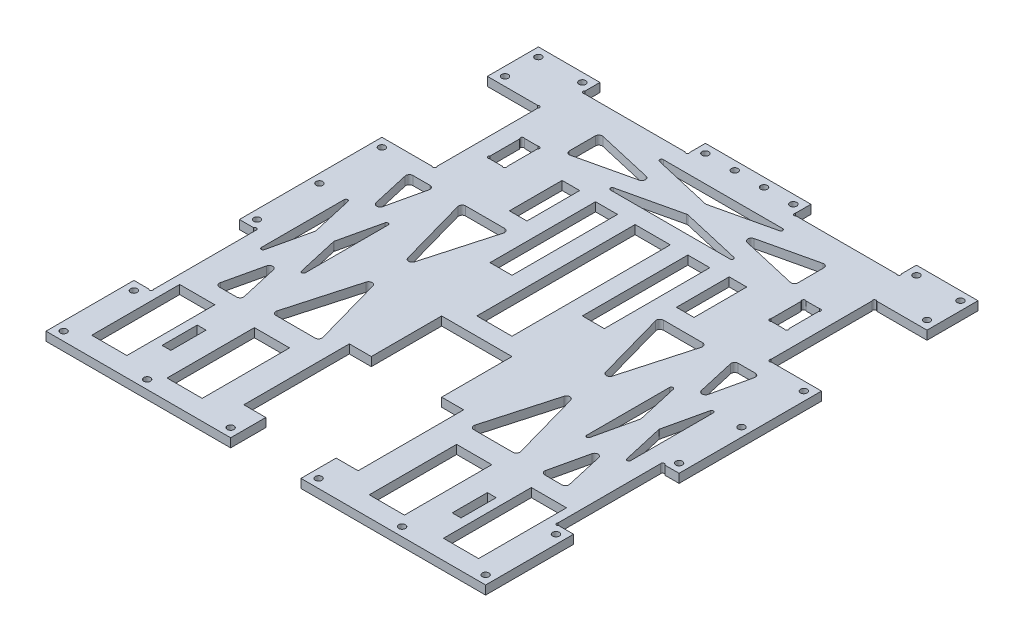
SolidWorks part; units mm, degrees
material "7050-T73510"
ref_plane "Front Plane" through (0, 0, 0) normal (0, 0, 1) x (1, 0, 0)
ref_plane "Top Plane" through (0, 0, 0) normal (0, 1, 0) x (1, 0, 0)
ref_plane "Right Plane" through (0, 0, 0) normal (1, 0, 0) x (0, 0, -1)
sketch "Sketch1" plane through (0, 0, 0) normal (0, 1, 0) x (1, 0, 0)
  line L1 (-158.75, -177.8) -> (158.75, -177.8)
  line L2 (-158.75, -177.8) -> (-158.75, 177.8)
  line L3 (-158.75, 177.8) -> (158.75, 177.8)
  line L4 (158.75, -177.8) -> (158.75, 177.8)
  line L5 (-158.75, -177.8) -> (158.75, 177.8) construction
  line L6 (-158.75, 177.8) -> (158.75, -177.8) construction
  point P0 (0, 0)
  dimension "D1" = 355.6
  dimension "D2" = 317.5
extrude "Boss-Extrude1" add sketch "Sketch1" along normal blind 6.35
sketch "Sketch2" plane through (0, 6.35, 0) normal (0, 1, 0) x (1, 0, 0)
  line L0 (-158.75, -177.8) -> (158.75, -177.8) construction
  line L1 (-25.4, -25.4) -> (25.4, -25.4)
  line L2 (-25.4, -25.4) -> (-25.4, -177.8)
  line L3 (-25.4, -177.8) -> (25.4, -177.8)
  line L4 (25.4, -25.4) -> (25.4, -177.8)
  line L5 (-25.4, -25.4) -> (25.4, -177.8) construction
  line L6 (-25.4, -177.8) -> (25.4, -25.4) construction
  point P0 (0, -101.6)
  dimension "D1" = 152.4
  dimension "D2" = 50.8
extrude "Cut-Extrude1" cut sketch "Sketch2" against normal through all
sketch "Sketch3" plane through (0, 6.35, 0) normal (0, 1, 0) x (1, 0, 0)
  line L0 (158.75, -177.8) -> (158.75, 177.8) construction
  line L5 (146.05, 140.97) -> (120.65, 140.97)
  line L11 (146.05, 140.97) -> (146.05, 64.77)
  line L13 (146.05, 64.77) -> (120.65, 64.77)
  line L15 (120.65, 140.97) -> (120.65, 64.77)
  line L16 (158.75, 177.8) -> (-158.75, 177.8) construction
  line L17 (107.95, 90.17) -> (95.25, 90.17)
  line L18 (107.95, 90.17) -> (107.95, 115.57)
  line L19 (107.95, 115.57) -> (95.25, 115.57)
  line L20 (95.25, 90.17) -> (95.25, 115.57)
  line L21 (0, -3.4925) -> (0, 3.4925) construction
  line L22 (-95.25, 90.17) -> (-95.25, 115.57)
  line L23 (-107.95, 115.57) -> (-95.25, 115.57)
  line L24 (-107.95, 90.17) -> (-107.95, 115.57)
  line L25 (-107.95, 90.17) -> (-95.25, 90.17)
  line L26 (-120.65, 140.97) -> (-120.65, 64.77)
  line L27 (-146.05, 64.77) -> (-120.65, 64.77)
  line L28 (-146.05, 140.97) -> (-146.05, 64.77)
  line L29 (-146.05, 140.97) -> (-120.65, 140.97)
  point P14 (107.95, 102.87)
  point P15 (120.65, 102.87)
  dimension "D1" = 25.4
  dimension "D2" = 12.7
  dimension "D3" = 12.7
  dimension "D4" = 12.7
  dimension "D5" = 25.4
  dimension "D6" = 76.2
  dimension "D7" = 36.83
extrude "Cut-Extrude2" cut sketch "Sketch3" against normal through all contours L5 L15 L13 L11 | L20 L17 L18 L19 | L29 L28 L27 L26 | L24 L25 L22 L23 | L26 L27 L28 L29 region at (133.35, 6.35, -102.87) region at (101.6, 6.35, -102.87) region at (-101.6, 6.35, -102.87) region at (-133.35, 6.35, -102.87)
sketch "Sketch4" plane through (0, 6.35, 0) normal (0, 1, 0) x (1, 0, 0)
  line L0 (-158.75, 177.8) -> (-158.75, -177.8) construction
  line L1 (-158.75, 140.97) -> (-146.05, 140.97)
  line L2 (-158.75, 140.97) -> (-158.75, 64.77)
  line L3 (-158.75, 64.77) -> (-146.05, 64.77)
  line L4 (-146.05, 140.97) -> (-146.05, 64.77)
  line L5 (0, -3.4925) -> (0, 3.4925) construction
  line L6 (-158.75, -114.3) -> (-146.05, -114.3)
  line L7 (-158.75, -114.3) -> (-158.75, -38.1)
  line L8 (-158.75, -38.1) -> (-146.05, -38.1)
  line L9 (-146.05, -114.3) -> (-146.05, -38.1)
  line L10 (158.75, 64.77) -> (146.05, 64.77)
  line L11 (146.05, 140.97) -> (146.05, 64.77)
  line L12 (158.75, 140.97) -> (146.05, 140.97)
  line L13 (158.75, 140.97) -> (158.75, 64.77)
  line L14 (158.75, -38.1) -> (146.05, -38.1)
  line L15 (146.05, -114.3) -> (146.05, -38.1)
  line L16 (158.75, -114.3) -> (146.05, -114.3)
  line L17 (158.75, -114.3) -> (158.75, -38.1)
  line L18 (158.75, 177.8) -> (-158.75, 177.8) construction
  line L19 (114.3, 165.1) -> (38.1, 165.1)
  line L20 (-114.3, 177.8) -> (-38.1, 177.8)
  line L21 (-114.3, 177.8) -> (-114.3, 165.1)
  line L22 (-114.3, 165.1) -> (-38.1, 165.1)
  line L23 (-38.1, 177.8) -> (-38.1, 165.1)
  line L24 (38.1, 177.8) -> (38.1, 165.1)
  line L25 (114.3, 177.8) -> (38.1, 177.8)
  line L26 (114.3, 177.8) -> (114.3, 165.1)
  line L27 (-25.4, -25.4) -> (-25.4, -177.8) construction
  line L28 (-25.4, -152.4) -> (-41.275, -152.4)
  line L29 (-25.4, -152.4) -> (-25.4, -76.2)
  line L30 (-25.4, -76.2) -> (-41.275, -76.2)
  line L31 (-41.275, -152.4) -> (-41.275, -76.2)
  line L32 (-158.75, -177.8) -> (-25.4, -177.8) construction
  line L33 (25.4, 101.6) -> (41.275, 101.6)
  line L34 (-25.4, 25.4) -> (-41.275, 25.4)
  line L35 (-25.4, 25.4) -> (-25.4, 101.6)
  line L36 (-25.4, 101.6) -> (-41.275, 101.6)
  line L37 (-41.275, 25.4) -> (-41.275, 101.6)
  line L38 (41.275, 25.4) -> (41.275, 101.6)
  line L39 (25.4, 25.4) -> (41.275, 25.4)
  line L40 (25.4, 25.4) -> (25.4, 101.6)
  line L41 (25.4, -76.2) -> (41.275, -76.2)
  line L42 (41.275, -152.4) -> (41.275, -76.2)
  line L43 (25.4, -152.4) -> (41.275, -152.4)
  line L44 (25.4, -152.4) -> (25.4, -76.2)
  dimension "D1" = 12.7
  dimension "D2" = 12.7
  dimension "D3" = 76.2
  dimension "D4" = 76.2
  dimension "D5" = 36.83
  dimension "D6" = 215.9
  dimension "D7" = 12.7
  dimension "D8" = 76.2
  dimension "D9" = 76.2
  dimension "D10" = 15.875
  dimension "D11" = 76.2
  dimension "D12" = 25.4
  dimension "D13" = 76.2
  dimension "D14" = 15.875
  dimension "D15" = 203.2
  dimension "D16" = 50.8
extrude "Cut-Extrude3" cut sketch "Sketch4" against normal through all
sketch "Sketch5" plane through (0, 6.35, 0) normal (0, 1, 0) x (1, 0, 0)
  line L0 (-41.275, -76.2) -> (-41.275, -152.4) construction
  line L5 (-41.275, 101.6) -> (-41.275, 25.4) construction
  line L6 (-85.725, -100.33) -> (-60.325, -100.33)
  line L7 (-133.35, -87.63) -> (-101.6, -87.63)
  line L8 (-133.35, -87.63) -> (-133.35, 52.07)
  line L9 (-133.35, 52.07) -> (-101.6, 52.07)
  line L10 (-101.6, -87.63) -> (-101.6, 52.07)
  line L11 (-133.35, -87.63) -> (-101.6, 52.07) construction
  line L12 (-133.35, 52.07) -> (-101.6, -87.63) construction
  line L13 (-82.55, 114.3) -> (82.55, 114.3)
  line L14 (-82.55, 114.3) -> (-82.55, 152.4)
  line L15 (-82.55, 152.4) -> (82.55, 152.4)
  line L16 (82.55, 114.3) -> (82.55, 152.4)
  line L17 (-82.55, 114.3) -> (82.55, 152.4) construction
  line L18 (-82.55, 152.4) -> (82.55, 114.3) construction
  line L23 (0, -3.4925) -> (0, 3.4925) construction
  line L24 (-12.7, -12.7) -> (12.7, -12.7)
  line L25 (-146.05, -114.3) -> (-146.05, -38.1) construction
  line L26 (-53.975, 102.87) -> (-66.675, 102.87)
  line L27 (-53.975, 102.87) -> (-53.975, 64.77)
  line L28 (-158.75, 64.77) -> (-158.75, -38.1) construction
  line L29 (-158.75, 64.77) -> (-120.65, 64.77) construction
  line L30 (-85.725, -100.33) -> (-85.725, -163.4194)
  line L31 (-12.7, -12.7) -> (-12.7, 101.6)
  line L32 (-12.7, 101.6) -> (12.7, 101.6)
  line L33 (12.7, -12.7) -> (12.7, 101.6)
  line L34 (-53.975, 64.77) -> (-66.675, 64.77)
  line L35 (-66.675, 102.87) -> (-66.675, 64.77)
  line L36 (53.975, 64.77) -> (66.675, 64.77)
  line L37 (-25.4, 25.4) -> (-25.4, 101.6) construction
  line L38 (-25.4, 101.6) -> (-41.275, 101.6) construction
  line L39 (-95.25, 90.17) -> (-95.25, 115.57) construction
  line L40 (-114.3, 165.1) -> (-38.1, 165.1) construction
  line L41 (-85.725, -163.4194) -> (-60.325, -163.4194)
  line L42 (-60.325, -100.33) -> (-60.325, -163.4194)
  line L43 (-139.5421, 50.6627) -> (-107.7921, -89.0373)
  line L44 (-127.1579, -89.0373) -> (-95.4079, 50.6627)
  line L45 (66.675, 102.87) -> (66.675, 64.77)
  line L46 (53.975, 102.87) -> (66.675, 102.87)
  line L47 (-83.9779, 146.2126) -> (81.1221, 108.1126)
  line L48 (-81.1221, 108.1126) -> (83.9779, 146.2126)
  line L49 (53.975, 102.87) -> (53.975, 64.77)
  line L50 (-88.9, -16.4414) -> (-53.975, -16.4414) construction
  line L51 (-127.1579, 53.4773) -> (-95.4079, -86.2227)
  line L52 (-139.5421, -86.2227) -> (-107.7921, 53.4773)
  line L53 (-88.9, 52.07) -> (-53.975, 52.07) construction
  line L54 (-88.9, 52.07) -> (-88.9, -84.9527) construction
  line L55 (-81.1221, 158.5874) -> (83.9779, 120.4874)
  line L56 (-83.9779, 120.4874) -> (81.1221, 158.5874)
  line L57 (-139.7, -100.33) -> (-114.3, -100.33)
  line L58 (-139.7, -100.33) -> (-139.7, -163.83)
  line L59 (-139.7, -163.83) -> (-114.3, -163.83)
  line L60 (-114.3, -100.33) -> (-114.3, -163.83)
  line L61 (-88.9, -84.9527) -> (-53.975, -84.9527)
  line L62 (-53.975, 52.07) -> (-53.975, -84.9527) construction
  line L63 (-107.95, -144.78) -> (-101.6, -144.78)
  line L64 (-107.95, -144.78) -> (-107.95, -119.38)
  line L65 (-107.95, -119.38) -> (-101.6, -119.38)
  line L66 (-101.6, -144.78) -> (-101.6, -119.38)
  line L67 (-107.95, -144.78) -> (-101.6, -119.38) construction
  line L68 (-107.95, -119.38) -> (-101.6, -144.78) construction
  line L69 (-88.9, -84.9527) -> (-71.4375, -22.7914)
  line L70 (-71.4375, -22.7914) -> (-53.975, -84.9527)
  line L71 (-88.9, 52.07) -> (-53.975, 52.07)
  line L72 (-88.9, 52.07) -> (-71.4375, -10.0914)
  line L73 (-71.4375, -10.0914) -> (-53.975, 52.07)
  point P5 (-117.475, -17.78)
  point P10 (0, 133.35)
  point P15 (0, 44.45)
  point P34 (-104.775, -132.08)
  point P45 (-33.3375, 101.6)
  point P87 (-114.3, -132.08)
  dimension "D3" = 12.7
  dimension "D4" = 19.05
  dimension "D5" = 139.7
  dimension "D6" = 25.4
  dimension "D7" = 12.7
  dimension "D8" = 31.75
  dimension "D9" = 25.4
  dimension "D10" = 12.7
  dimension "D11" = 165.1
  dimension "D12" = 12.7
  dimension "D13" = 12.7
  dimension "D14" = 12.7
  dimension "D17" = 25.4
  dimension "D18" = 63.5
  dimension "D19" = 12.7
  dimension "D20" = 6.35
  dimension "D21" = 38.1
  dimension "D22" = 38.1
  dimension "D23" = 25.4
  dimension "D15" = 114.3
  dimension "D16" = 12.7
  dimension "D24" = 12.7
  dimension "D25" = 12.7
  dimension "D26" = 12.7
  dimension "D27" = 15.3773
  dimension "D28" = 12.7
  dimension "D29" = 6.35
  dimension "D30" = 12.7
extrude "Cut-Extrude4" cut sketch "Sketch5" against normal through all contours L44 L7 L43 | L8 L52 L43 | L51 L52 L9 | L44 L51 L10 | L33 | L32 | L31 | L24 | L48 L13 L47 | L48 L55 L16 | L55 L56 L15 | L14 L56 L47 | L60 L57 L58 L59 | L63 L66 L65 L64 | L42 L6 L30 L41 | L26 L35 L34 L27 | L46 L49 L36 L45 | L61 L70 L69 | L71 L73 L72 region at (-73.025, 6.35, 131.8747) region at (-117.475, 6.35, 73.8975) region at (-130.229, 6.35, 17.78) region at (-104.721, 6.35, 17.78) region at (-117.475, 6.35, -38.3375) region at (0, 6.35, -118.4777) region at (-64.4466, 6.35, -133.35) region at (64.4466, 6.35, -133.35) region at (0, 6.35, -148.2223) region at (0, 6.35, -44.45) region at (-60.325, 6.35, -83.82) region at (60.325, 6.35, -83.82) region at (-127, 6.35, 132.08) region at (-104.775, 6.35, 132.08)
mirror "Mirror1" about plane through (0, 0, 0) normal (1, 0, 0) of "Cut-Extrude4"
sketch "Sketch7" plane through (0, 6.35, 0) normal (0, 1, 0) x (1, 0, 0)
  line L0 (-158.75, -177.8) -> (-25.4, -177.8) construction
  line L1 (-158.75, -114.3) -> (-158.75, -177.8) construction
  line L2 (0, -3.4925) -> (0, 3.4925) construction
  line L3 (-158.75, 177.8) -> (-158.75, 140.97) construction
  line L4 (-114.3, 177.8) -> (-158.75, 177.8) construction
  line L6 (38.1, 177.8) -> (-38.1, 177.8) construction
  line L7 (-38.1, 165.1) -> (-38.1, 177.8) construction
  line L8 (-25.4, -152.4) -> (-25.4, -177.8) construction
  line L9 (-158.75, -114.3) -> (-146.05, -114.3) construction
  line L10 (-158.75, 64.77) -> (-158.75, -38.1) construction
  line L11 (-146.05, -38.1) -> (-158.75, -38.1) construction
  line L12 (-158.75, 64.77) -> (-120.65, 64.77) construction
  circle A0 centre (-152.4, -171.45) radius 2.413
  circle A14 centre (-152.4, 171.45) radius 2.413
  circle A15 centre (-120.65, 171.45) radius 2.413
  circle A16 centre (-152.4, 147.32) radius 2.413
  circle A34 centre (-31.75, 171.45) radius 2.413
  circle A35 centre (-10.5833, 171.45) radius 2.413
  circle A36 centre (10.5833, 171.45) radius 2.413
  circle A37 centre (31.75, 171.45) radius 2.413
  circle A38 centre (-31.75, -171.45) radius 2.413
  circle A39 centre (-92.075, -171.45) radius 2.413
  circle A40 centre (-152.4, -120.65) radius 2.413
  circle A41 centre (-152.4, -31.75) radius 2.413
  circle A42 centre (-152.4, 58.42) radius 2.413
  circle A43 centre (-152.4, 13.335) radius 2.413
  circle A44 centre (31.75, -171.45) radius 2.413
  circle A45 centre (152.4, 13.335) radius 2.413
  circle A46 centre (152.4, 58.42) radius 2.413
  circle A47 centre (152.4, -31.75) radius 2.413
  circle A48 centre (152.4, -120.65) radius 2.413
  circle A49 centre (92.075, -171.45) radius 2.413
  circle A50 centre (152.4, 147.32) radius 2.413
  circle A51 centre (120.65, 171.45) radius 2.413
  circle A52 centre (152.4, 171.45) radius 2.413
  circle A53 centre (152.4, -171.45) radius 2.413
  dimension "D1" = 4.826
  dimension "D6" = 6.35
  dimension "D9" = 4.826
  dimension "D14" = 4.826
  dimension "D4" = 4.826
  dimension "D5" = 4.826
  dimension "D8" = 4.826
  dimension "D20" = 4.826
  dimension "D24" = 4.826
  dimension "D25" = 4.826
  dimension "D2" = 6.35
  dimension "D3" = 6.35
  dimension "D7" = 60.325
  dimension "D10" = 6.35
  dimension "D11" = 6.35
  dimension "D15" = 6.35
  dimension "D16" = 6.35
  dimension "D18" = 6.35
  dimension "D19" = 6.35
  dimension "D21" = 6.35
  dimension "D22" = 6.35
  dimension "D23" = 6.35
  dimension "D26" = 45.085
  dimension "D12" = 2
  dimension "D13" = 2
  dimension "D17" = 4
extrude "Cut-Extrude6" cut sketch "Sketch7" against normal through all
sketch "Sketch8" plane through (0, 6.35, 0) normal (0, 1, 0) x (1, 0, 0)
  circle A0 centre (-39.0994, 165.8837) radius 1.27
  circle A1 centre (-113.5398, 166.1174) radius 1.27
  circle A2 centre (-121.56, 140.0841) radius 1.27
  circle A3 centre (-121.5656, 65.6501) radius 1.27
  circle A4 centre (-147.253, -38.507) radius 1.27
  circle A5 centre (-147.0444, -113.51) radius 1.27
  circle A6 centre (-107.1943, 114.5493) radius 1.27
  circle A7 centre (-96.0341, 114.5709) radius 1.27
  circle A8 centre (-107.1845, 91.1833) radius 1.27
  circle A10 centre (-96.2084, 91.0033) radius 1.27
extrude "Cut-Extrude7" cut sketch "Sketch8" against normal through all
mirror "Mirror2" about plane through (0, 0, 0) normal (1, 0, 0) of "Cut-Extrude7"
fillet "Fillet1" radius 1.27 16 edges at (-101.6, 3.175, 58.9775) (-110.9631, 3.175, 17.78) (-101.6, 3.175, -23.4175) (-133.35, 3.175, -23.4175) (-123.9869, 3.175, 17.78) (-133.35, 3.175, 58.9775) (133.35, 3.175, -23.4175) (133.35, 3.175, 58.9775) (123.9869, 3.175, 17.78) (101.6, 3.175, -23.4175) (110.9631, 3.175, 17.78) (101.6, 3.175, 58.9775) (54.3101, 3.175, -152.4) (-54.3101, 3.175, -152.4) (54.3101, 3.175, -114.3) (-54.3101, 3.175, -114.3)
fillet "Fillet2" radius 2.54 32 edges at (-126.8381, 3.175, 87.63) (-108.1119, 3.175, 87.63) (-117.475, 3.175, 46.4325) (-28.2399, 3.175, -133.35) (-82.55, 3.175, -120.8169) (-82.55, 3.175, -145.8831) (-88.9, 3.175, -52.07) (-71.4375, 3.175, 10.0914) (-53.975, 3.175, -52.07) (-71.4375, 3.175, 22.7914) (-88.9, 3.175, 84.9527) (-53.975, 3.175, 84.9527) (-126.8381, 3.175, -52.07) (-117.475, 3.175, -10.8725) (-108.1119, 3.175, -52.07) (126.8381, 3.175, 87.63) (108.1119, 3.175, 87.63) (117.475, 3.175, 46.4325) (88.9, 3.175, 84.9527) (53.975, 3.175, 84.9527) (71.4375, 3.175, 22.7914) (117.475, 3.175, -10.8725) (108.1119, 3.175, -52.07) (126.8381, 3.175, -52.07) (71.4375, 3.175, 10.0914) (88.9, 3.175, -52.07) (53.975, 3.175, -52.07) (28.2399, 3.175, -133.35) (82.55, 3.175, -120.8169) (82.55, 3.175, -145.8831) (0, 3.175, -139.8669) (0, 3.175, -126.8331)
